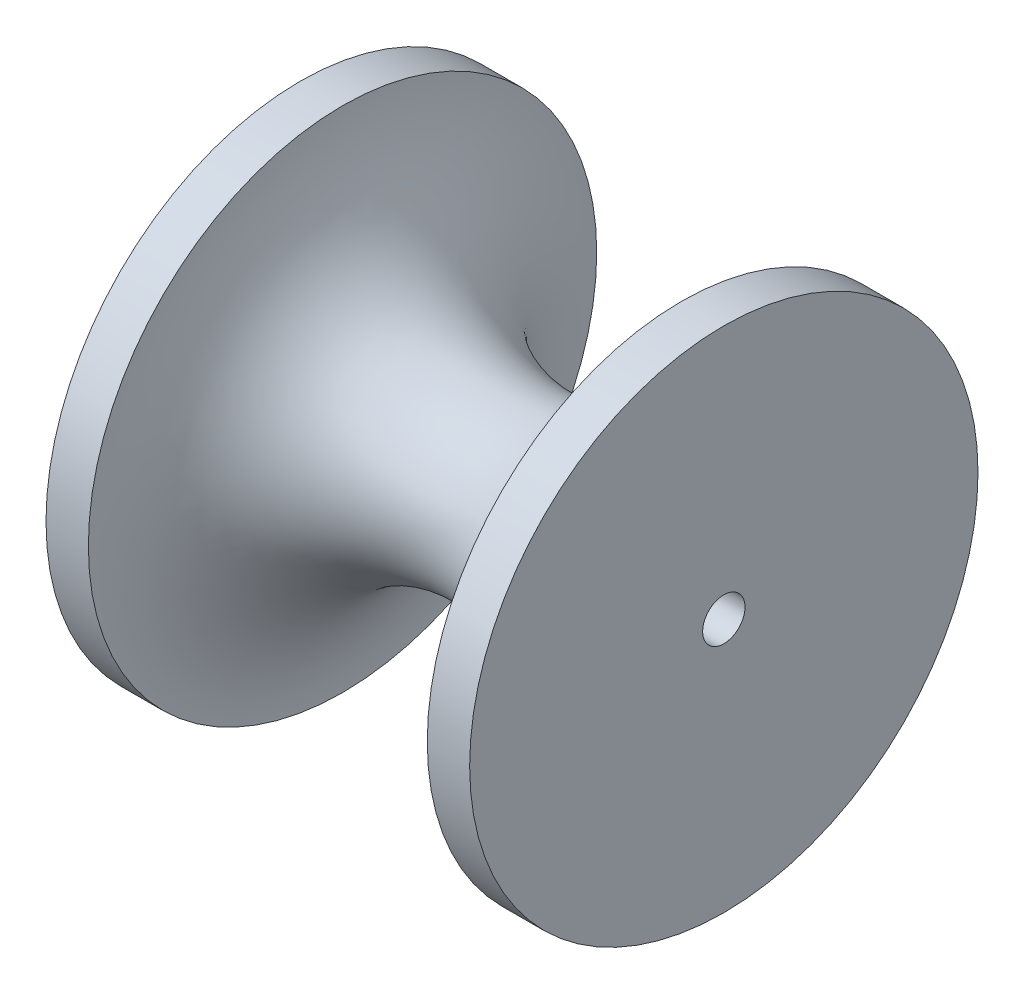
SolidWorks part; units mm, degrees
ref_plane "Front Plane" through (0, 0, 0) normal (0, 0, 1) x (1, 0, 0)
ref_plane "Top Plane" through (0, 0, 0) normal (0, 1, 0) x (1, 0, 0)
ref_plane "Right Plane" through (0, 0, 0) normal (1, 0, 0) x (0, 0, -1)
sketch "Sketch1" plane through (0, 0, 0) normal (0, 0, 1) x (1, 0, 0)
  line L0 (-12.5, 0) -> (12.5, 0)
  line L5 (-12.5, 15) -> (12.5, 15)
  line L10 (12.5, 15) -> (12.5, 0)
  line L14 (-12.5, 15) -> (-12.5, 0)
  arc A1 (-10, 15) -> (10, 15) centre (0, 15) ccw
  point P3 (0, 0)
  dimension "D3" = 10
  dimension "D1" = 15
  dimension "D2" = 25
revolve "Revolve1" add sketch "Sketch1" angle 360 about L0 region at (-12.2085, 7.5, 0)
sketch "Sketch2" plane through (12.5, 0, 0) normal (1, 0, 0) x (0, 0, -1)
  line L0 (0, 37.5) -> (0, -37.5) construction
  circle A1 centre (0, 0) radius 1.25
  point P7 (0, 0)
  point P8 (0, 0)
  dimension "D1" = 2.5
extrude "Cut-Extrude1" cut sketch "Sketch2" against normal through all
